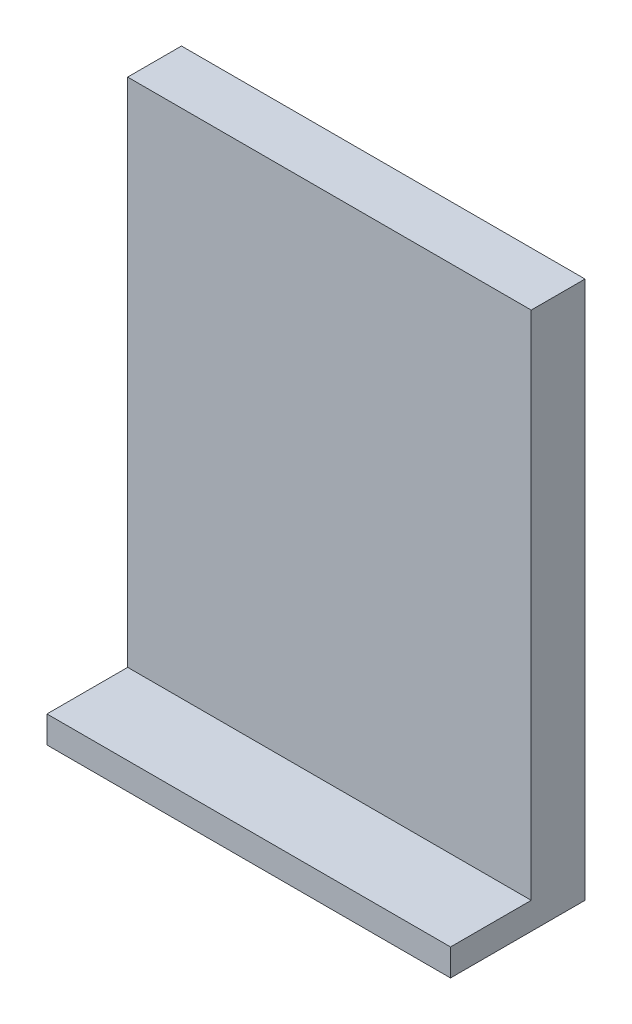
SolidWorks part; units mm, degrees
ref_plane "Front Plane" through (0, 0, 0) normal (0, 0, 1) x (1, 0, 0)
ref_plane "Top Plane" through (0, 0, 0) normal (0, 1, 0) x (1, 0, 0)
ref_plane "Right Plane" through (0, 0, 0) normal (1, 0, 0) x (0, 0, -1)
sketch "Sketch1" plane through (0, 0, 0) normal (0, 0, 1) x (1, 0, 0)
  line L1 (11.5464, 17.872) -> (26.5464, 17.872)
  line L2 (11.5464, 17.872) -> (11.5464, -2.128)
  line L3 (11.5464, -2.128) -> (26.5464, -2.128)
  line L4 (26.5464, 17.872) -> (26.5464, -2.128)
  dimension "D1" = 15
  dimension "D2" = 20
extrude "Boss-Extrude1" add sketch "Sketch1" along normal blind 2
sketch "Sketch3" plane through (0, 0, 2) normal (0, 0, 1) x (1, 0, 0)
  line L0 (26.5464, -2.128) -> (26.5464, 17.872) construction
  line L1 (11.5464, -2.128) -> (26.5464, -2.128)
  line L2 (11.5464, -2.128) -> (11.5464, -1.128)
  line L3 (11.5464, -1.128) -> (26.5464, -1.128)
  line L4 (26.5464, -2.128) -> (26.5464, -1.128)
  dimension "D1" = 1
extrude "Boss-Extrude2" add sketch "Sketch3" along normal blind 3
